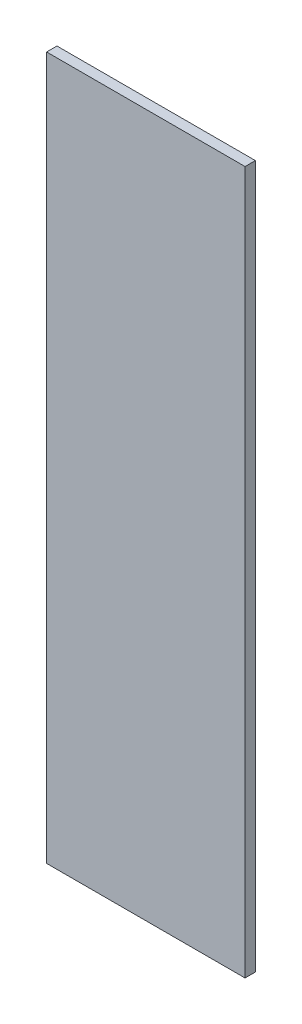
SolidWorks part; units mm, degrees
material "PC High Viscosity"
ref_plane "Front Plane" through (0, 0, 0) normal (0, 0, 1) x (1, 0, 0)
ref_plane "Top Plane" through (0, 0, 0) normal (0, 1, 0) x (1, 0, 0)
ref_plane "Right Plane" through (0, 0, 0) normal (1, 0, 0) x (0, 0, -1)
sketch "Sketch1" plane through (0, 0, 0) normal (0, 0, 1) x (1, 0, 0)
  line L1 (-48, -200) -> (48, -200)
  line L2 (-48, -200) -> (-48, 200)
  line L3 (-48, 200) -> (48, 200)
  line L4 (48, -200) -> (48, 200)
  line L5 (-48, -200) -> (48, 200) construction
  line L6 (-48, 200) -> (48, -200) construction
  point P0 (0, 0)
  dimension "D1" = 96
  dimension "D2" = 400
extrude "Boss-Extrude1" add sketch "Sketch1" along normal mid plane 5
sketch "Sketch2" plane through (0, 0, 2.5) normal (0, 0, 1) x (1, 0, 0)
  line L0 (106, 140) -> (104, 140) construction
  line L1 (-155.214, 211.8255) -> (203.9552, 211.8255)
  line L2 (-155.214, 211.8255) -> (-155.214, 140)
  line L3 (-155.214, 140) -> (203.9552, 140)
  line L4 (203.9552, 211.8255) -> (203.9552, 140)
extrude "Cut-Extrude1" cut sketch "Sketch2" against normal through all
